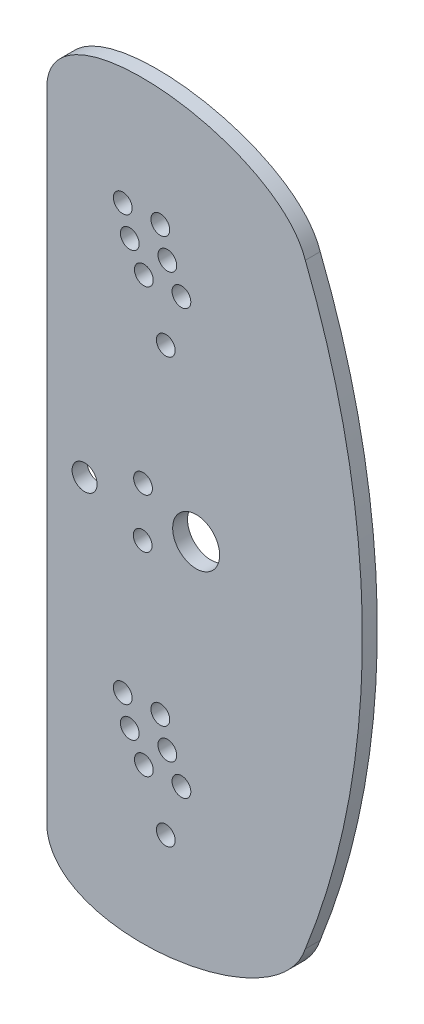
SolidWorks part; units mm, degrees
ref_plane "Front Plane" through (0, 0, 0) normal (0, 0, 1) x (1, 0, 0)
ref_plane "Top Plane" through (0, 0, 0) normal (0, 1, 0) x (1, 0, 0)
ref_plane "Right Plane" through (0, 0, 0) normal (1, 0, 0) x (0, 0, -1)
sketch "Sketch1" plane through (0, 0, 0) normal (0, 1, 0) x (1, 0, 0)
  line L0 (-92.9216, 89.0184) -> (669.0784, 89.0184)
  line L1 (669.0784, 89.0184) -> (669.0784, 419.2184)
  line L2 (-92.9216, 89.0184) -> (-92.9216, 419.2184)
  line L5 (110.2784, 495.4184) -> (465.8784, 495.4184)
  line L8 (110.2784, 495.4184) -> (-92.9216, 419.2184)
  line L9 (465.8784, 495.4184) -> (669.0784, 419.2184)
  line L10 (-92.9216, 495.4184) -> (669.0784, 495.4184) construction
sketch "Sketch2" plane through (0, 0, 0) normal (0, 0, 1) x (1, 0, 0)
  line L0 (1361.0966, 1819.7347) -> (1361.0966, 996.3635)
  line L1 (1361.0966, 1789.0491) -> (1361.0966, 1027.0491)
  arc A0 (1691.2966, 1027.0491) -> (1691.2966, 1789.0491) centre (733.0004, 1408.0491) ccw
  circle A1 centre (1506.0488, 1194.0197) radius 12
  circle A2 centre (1515.0488, 1159.0198) radius 12
  circle A3 centre (1533.0488, 1127.7698) radius 12
  circle A4 centre (1467.0488, 1159.0198) radius 12
  circle A5 centre (1485.0488, 1127.7698) radius 12
  circle A6 centre (1458.0488, 1194.0197) radius 12
  circle A7 centre (1513.0482, 1064.0197) radius 12
  circle A8 centre (1506.0488, 1735.9899) radius 12
  circle A9 centre (1515.0488, 1700.99) radius 12
  circle A10 centre (1533.0488, 1669.74) radius 12
  circle A11 centre (1467.0488, 1700.99) radius 12
  circle A12 centre (1485.0488, 1669.74) radius 12
  circle A13 centre (1458.0488, 1735.9899) radius 12
  circle A14 centre (1513.0482, 1605.9899) radius 12
  circle A15 centre (1483.5084, 1375.1967) radius 12
  circle A16 centre (1483.9827, 1438.6917) radius 12
  circle A17 centre (1551.8392, 1408.0266) radius 29.9999
  circle A18 centre (1409.3368, 1408.0266) radius 15.9995
  spline S0 degree 3 poles (1691.2966, 1027.0491) (1656.7077, 922.0591) (1371.3251, 886.2968) (1361.0966, 996.3635) knots 0 0 0 0 7.629784 7.629784 7.629784 7.629784
  spline S1 degree 3 poles (1691.2966, 1789.0491) (1656.7629, 1894.0573) (1371.3251, 1929.8013) (1361.0966, 1819.7347) knots 0 0 0 0 7.638295 7.638295 7.638295 7.638295
extrude "Boss-Extrude3" add sketch "Sketch2" along normal blind 19.05 separate body contours A0 S1 L0 S0 A1 A2 A3 A4 A5 A6 A7 A8 A9 A10 A11 A12 A13 A14 A15 A16 A17 A18 region at (1526.2742, 1873.438, 0)
